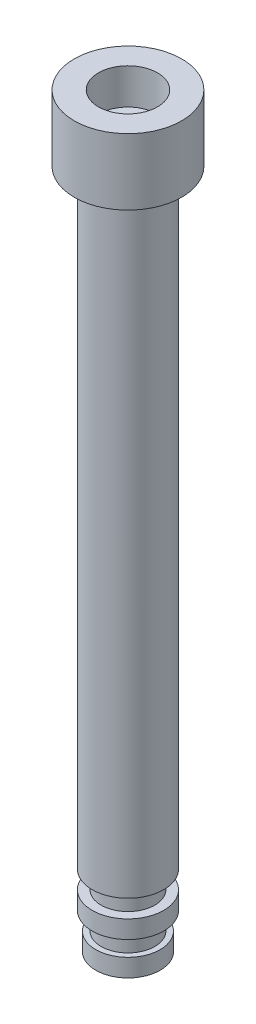
SolidWorks part; units mm, degrees
ref_plane "Front Plane" through (0, 0, 0) normal (0, 0, 1) x (1, 0, 0)
ref_plane "Top Plane" through (0, 0, 0) normal (0, 1, 0) x (1, 0, 0)
ref_plane "Right Plane" through (0, 0, 0) normal (1, 0, 0) x (0, 0, -1)
sketch "Sketch1" plane through (0, 0, 0) normal (0, 1, 0) x (1, 0, 0)
  circle A0 centre (-0.522, 0.5111) radius 1.6
  circle A1 centre (-0.522, 0.5111) radius 3
  dimension "D1" = 3.2
  dimension "D2" = 6
extrude "Boss-Extrude1" add sketch "Sketch1" along normal blind 3.7 contours A1
extrude "Boss-Extrude2" add sketch "Sketch1<3>" along normal blind 1 contours A0 region at (-0.522, 0, -0.5111)
sketch "Sketch1<3>" plane through (0, 0, 0) normal (0, 1, 0) x (1, 0, 0) same geometry as "Sketch1"
sketch "Sketch5" plane through (0, 0, 0) normal (0, -1, 0) x (1, 0, 0)
  circle A2 centre (-0.522, -0.5111) radius 1.5
  circle A3 centre (-0.522, -0.5111) radius 1.5
  dimension "D2" = 3
  dimension "D1" = 1.5
extrude "Boss-Extrude3" add sketch "Sketch5" along normal blind 35 contours A3
sketch "Sketch6" plane through (0, -35, 0) normal (0, -1, 0) x (1, 0, 0)
  circle A0 centre (-0.522, -0.5111) radius 2
  dimension "D1" = 4
extrude "Boss-Extrude4" add sketch "Sketch6" along normal blind 1
sketch "Sketch8" plane through (0, -36, 0) normal (0, -1, 0) x (-1, 0, 0)
  circle A0 centre (0.522, 0.5111) radius 1.5
  dimension "D1" = 3
extrude "Boss-Extrude5" add sketch "Sketch8" along normal blind 2 contours A0
sketch "Sketch10" plane through (0, -38, 0) normal (0, -1, 0) x (1, 0, 0)
  circle A0 centre (-0.522, -0.5111) radius 1.8
extrude "Boss-Extrude6" add sketch "Sketch10" against normal blind 1
sketch "Sketch11" plane through (0, 3.7, 0) normal (0, 1, 0) x (1, 0, 0)
  text T0 "VIII" font "Century Gothic" height in points 5
sketch "Sketch12" plane through (0, 3.7, 0) normal (0, 1, 0) x (1, 0, 0)
  circle A0 centre (-0.522, 0.5111) radius 1.65
extrude "Cut-Extrude1" cut sketch "Sketch12" against normal blind 2
sketch "Sketch13" plane through (0, 0, 0) normal (0, -1, 0) x (1, 0, 0)
  circle A0 centre (-0.522, -0.5111) radius 2
extrude "Boss-Extrude7" add sketch "Sketch13" along normal blind 34
